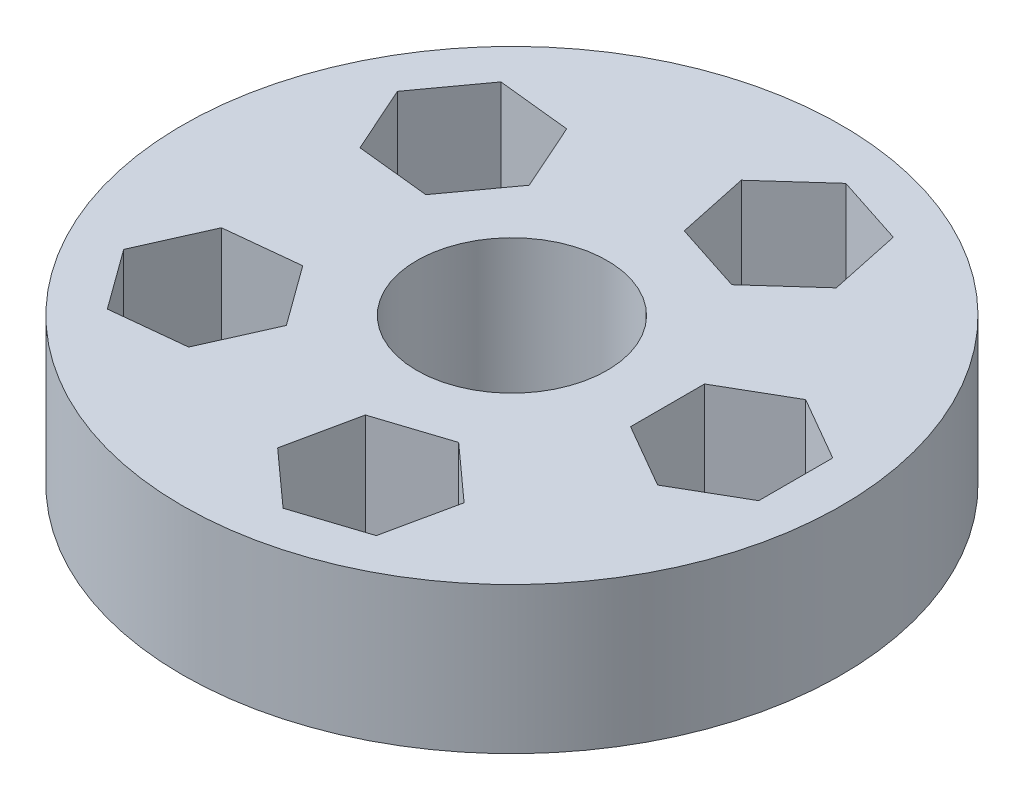
SolidWorks part; units mm, degrees
material "6061 Alloy"
ref_plane "Front Plane" through (0, 0, 0) normal (0, 0, 1) x (1, 0, 0)
ref_plane "Top Plane" through (0, 0, 0) normal (0, 1, 0) x (1, 0, 0)
ref_plane "Right Plane" through (0, 0, 0) normal (1, 0, 0) x (0, 0, -1)
sketch "Sketch1" plane through (0, 0, 0) normal (0, 1, 0) x (1, 0, 0)
  circle A0 centre (0, 0) radius 28.575
  circle A1 centre (0, 0) radius 19.05 construction
  circle A2 centre (0, 0) radius 8.255
  circle A3 centre (19.05, 0) radius 3.2004
  circle A4 centre (5.8868, -18.1176) radius 3.2004
  circle A5 centre (-15.4118, -11.1973) radius 3.2004
  circle A6 centre (-15.4118, 11.1973) radius 3.2004
  circle A7 centre (5.8868, 18.1176) radius 3.2004
  point P18 (0, 0)
  dimension "D1" = 57.15
  dimension "D2" = 38.1
  dimension "D3" = 16.51
  dimension "D4" = 6.4008
  dimension "D5" = 5
extrude "Boss-Extrude1" add sketch "Sketch1" along normal blind 12.7
sketch "Sketch2" plane through (0, 12.7, 0) normal (0, 1, 0) x (1, 0, 0)
  line L0 (5.8868, 18.1176) -> (0, 0) construction
  line L1 (1.1189, 13.8246) -> (7.2207, 11.842)
  line L2 (7.2207, 11.842) -> (11.9886, 16.135)
  line L3 (11.9886, 16.135) -> (10.6546, 22.4106)
  line L4 (10.6546, 22.4106) -> (4.5529, 24.3932)
  line L5 (4.5529, 24.3932) -> (-0.215, 20.1002)
  line L6 (-0.215, 20.1002) -> (1.1189, 13.8246)
  line L7 (13.4938, 3.2079) -> (13.4938, -3.2079)
  line L8 (13.4938, -3.2079) -> (19.05, -6.4158)
  line L9 (19.05, -6.4158) -> (24.6063, -3.2079)
  line L10 (24.6063, -3.2079) -> (24.6063, 3.2079)
  line L11 (24.6063, 3.2079) -> (19.05, 6.4158)
  line L12 (19.05, 6.4158) -> (13.4938, 3.2079)
  line L13 (7.2207, -11.842) -> (1.1189, -13.8246)
  line L14 (1.1189, -13.8246) -> (-0.215, -20.1002)
  line L15 (-0.215, -20.1002) -> (4.5529, -24.3932)
  line L16 (4.5529, -24.3932) -> (10.6546, -22.4106)
  line L17 (10.6546, -22.4106) -> (11.9886, -16.135)
  line L18 (11.9886, -16.135) -> (7.2207, -11.842)
  line L19 (-9.0311, -10.5267) -> (-12.8022, -5.3362)
  line L20 (-12.8022, -5.3362) -> (-19.1829, -6.0068)
  line L21 (-19.1829, -6.0068) -> (-21.7924, -11.8679)
  line L22 (-21.7924, -11.8679) -> (-18.0213, -17.0584)
  line L23 (-18.0213, -17.0584) -> (-11.6407, -16.3878)
  line L24 (-11.6407, -16.3878) -> (-9.0311, -10.5267)
  line L25 (-12.8022, 5.3362) -> (-9.0311, 10.5267)
  line L26 (-9.0311, 10.5267) -> (-11.6407, 16.3878)
  line L27 (-11.6407, 16.3878) -> (-18.0213, 17.0584)
  line L28 (-18.0213, 17.0584) -> (-21.7924, 11.8679)
  line L29 (-21.7924, 11.8679) -> (-19.1829, 6.0068)
  line L30 (-19.1829, 6.0068) -> (-12.8022, 5.3362)
  circle A0 centre (5.8868, 18.1176) radius 5.5562 construction
  circle A1 centre (0, 0) radius 19.05 construction
  circle A2 centre (19.05, 0) radius 5.5563 construction
  circle A3 centre (5.8868, -18.1176) radius 5.5562 construction
  circle A4 centre (-15.4118, -11.1973) radius 5.5562 construction
  circle A5 centre (-15.4118, 11.1973) radius 5.5563 construction
  point P10 (4.1698, 12.8333)
  point P48 (0, 0)
  dimension "D1" = 11.1125
  dimension "D2" = 38.1
  dimension "D3" = 5
extrude "Cut-Extrude1" cut sketch "Sketch2" against normal blind 9.525
chamfer "Chamfer1" [suppressed] distance 2.54 angle 60
